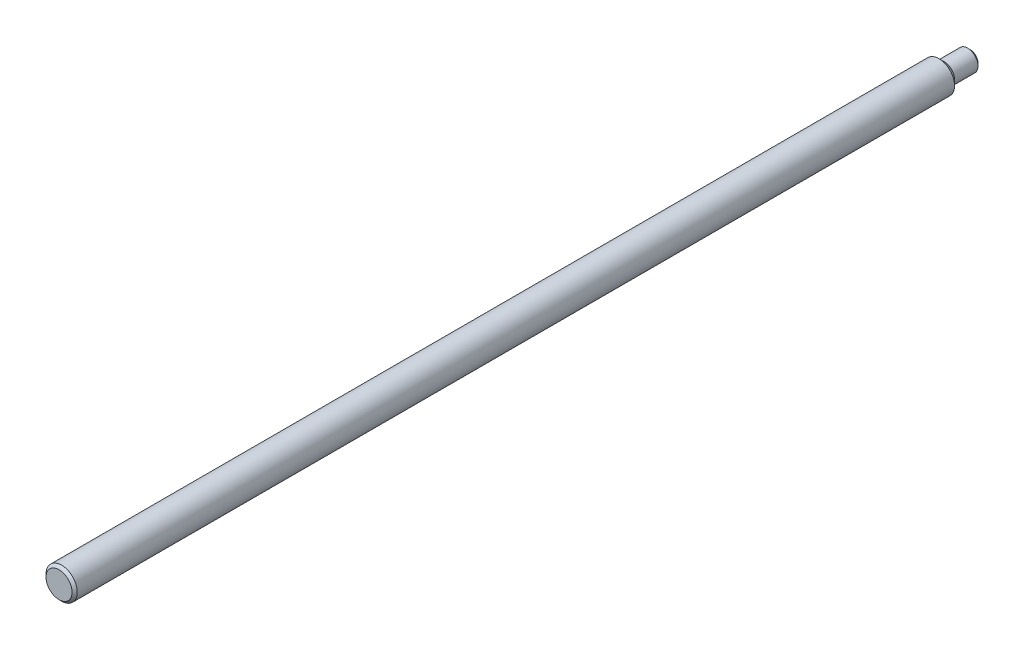
SolidWorks part; units mm, degrees
ref_plane "Piano frontale" through (0, 0, 0) normal (0, 0, 1) x (1, 0, 0)
ref_plane "Piano superiore" through (0, 0, 0) normal (0, 1, 0) x (1, 0, 0)
ref_plane "Piano destro" through (0, 0, 0) normal (1, 0, 0) x (0, 0, -1)
sketch "Schizzo1" plane through (0, 0, 0) normal (0, 0, 1) x (1, 0, 0)
  circle A0 centre (0, 0) radius 6
  dimension "D1" = 12
extrude "Estrusione-Estrusione1" add sketch "Schizzo1" along normal blind 350
cosmetic thread "Filettatura cosmetica1" parameters "D2"=10.344
sketch "Schizzo2" plane through (0, 0, 0) normal (0, 1, 0) x (1, 0, 0)
  line L0 (0, 1.8987) -> (0, -61.2971) construction
  line L1 (-4, -10) -> (-6, -12)
  line L2 (-6, -12) -> (-6, 0)
  line L3 (-6, 0) -> (-4, 0)
  line L4 (-4, 0) -> (-4, -10)
  line L5 (-6, 0) -> (-6, -350) construction
  line L6 (6, 0) -> (-6, 0) construction
  dimension "D1" = 8
  dimension "D2" = 135
  dimension "D3" = 10
revolve "Taglia-Rivoluzione1" cut sketch "Schizzo2" angle 360 about L0
chamfer "Smusso1" distance 1 angle 45 2 edges at (-4, 0, 0) (6, 0, 350)
sketch "Schizzo3" plane through (0, 0, 0) normal (0, 1, 0) x (1, 0, 0)
  line L0 (-4, -10) -> (-4, -10.2926)
